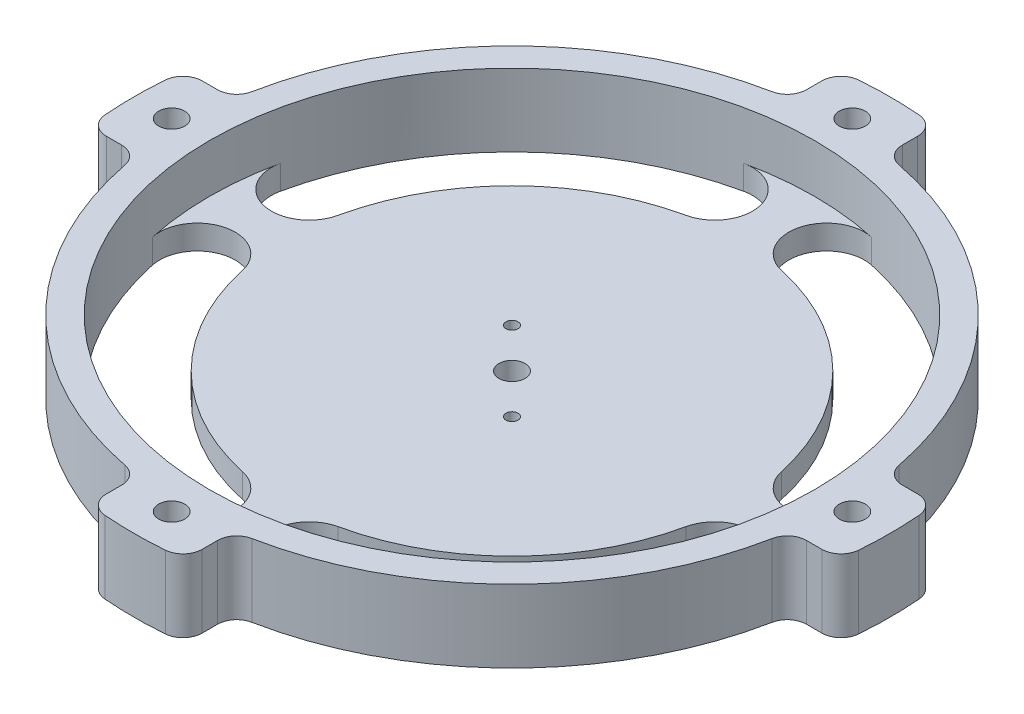
SolidWorks part; units mm, degrees
material "Nylon 101"
ref_plane "Front Plane" through (0, 0, 0) normal (0, 0, 1) x (1, 0, 0)
ref_plane "Top Plane" through (0, 0, 0) normal (0, 1, 0) x (1, 0, 0)
ref_plane "Right Plane" through (0, 0, 0) normal (1, 0, 0) x (0, 0, -1)
sketch "Sketch1" plane through (0, 0, 0) normal (0, 0, 1) x (1, 0, 0)
  line L0 (0, 0) -> (0, 12) construction
  line L1 (0, 0) -> (62.5, 0)
  line L2 (62.5, 0) -> (62.5, 12)
  line L3 (62.5, 12) -> (50, 12)
  line L4 (50, 12) -> (50, 4)
  line L5 (50, 4) -> (0, 4)
  line L6 (0, 4) -> (0, 0)
  dimension "D1" = 100
  dimension "D2" = 4
  dimension "D3" = 125
  dimension "D4" = 12
revolve "Revolve1" add sketch "Sketch1" angle 360 about L0
sketch "Sketch2" plane through (0, 4, 0) normal (0, 1, 0) x (1, 0, 0)
  line L0 (6.5407, -6.5407) -> (-6.5407, 6.5407) construction
  line L1 (0, 0) -> (-6.5407, 0) construction
  circle A0 centre (0, 0) radius 2
  circle A1 centre (6.5407, -6.5407) radius 1
  circle A2 centre (-6.5407, 6.5407) radius 1
  dimension "D1" = 4
  dimension "D3" = 2
  dimension "D2" = 18.5
  dimension "D4" = 45
extrude "Cut-Extrude1" cut sketch "Sketch2" against normal up to next
sketch "Sketch3" plane through (0, 4, 0) normal (0, 1, 0) x (1, 0, 0)
  line L0 (0, 0) -> (0, 62.5) construction
  line L1 (0, 0) -> (62.5, 0) construction
  line L2 (3, 42.761) -> (0, 42.761) construction
  line L3 (42.761, 3) -> (42.761, 0) construction
  circle A0 centre (0, 0) radius 37.5 construction
  circle A1 centre (0, 0) radius 62.5 construction
  arc A2 (9.25, 42.761) -> (42.761, 9.25) centre (0, 0) cw construction
  arc A3 (48.8697, 10.5714) -> (10.5714, 48.8697) centre (0, 0) ccw
  arc A4 (36.6523, 7.9286) -> (7.9286, 36.6523) centre (0, 0) ccw
  arc A5 (36.6523, 7.9286) -> (48.8697, 10.5714) centre (42.761, 9.25) ccw
  arc A6 (10.5714, 48.8697) -> (7.9286, 36.6523) centre (9.25, 42.761) ccw
  circle A7 centre (0, 0) radius 50 construction
  arc A8 (-9.25, 42.761) -> (-42.761, 9.25) centre (0, 0) ccw construction
  arc A9 (-48.8697, 10.5714) -> (-10.5714, 48.8697) centre (0, 0) cw
  arc A10 (-36.6523, 7.9286) -> (-7.9286, 36.6523) centre (0, 0) cw
  arc A11 (-36.6523, 7.9286) -> (-48.8697, 10.5714) centre (-42.761, 9.25) cw
  arc A12 (-10.5714, 48.8697) -> (-7.9286, 36.6523) centre (-9.25, 42.761) cw
  arc A13 (9.25, -42.761) -> (42.761, -9.25) centre (0, 0) ccw construction
  arc A14 (48.8697, -10.5714) -> (10.5714, -48.8697) centre (0, 0) cw
  arc A15 (36.6523, -7.9286) -> (7.9286, -36.6523) centre (0, 0) cw
  arc A16 (36.6523, -7.9286) -> (48.8697, -10.5714) centre (42.761, -9.25) cw
  arc A17 (10.5714, -48.8697) -> (7.9286, -36.6523) centre (9.25, -42.761) cw
  arc A18 (-9.25, -42.761) -> (-42.761, -9.25) centre (0, 0) cw construction
  arc A19 (-48.8697, -10.5714) -> (-10.5714, -48.8697) centre (0, 0) ccw
  arc A20 (-36.6523, -7.9286) -> (-7.9286, -36.6523) centre (0, 0) ccw
  arc A21 (-36.6523, -7.9286) -> (-48.8697, -10.5714) centre (-42.761, -9.25) ccw
  arc A22 (-10.5714, -48.8697) -> (-7.9286, -36.6523) centre (-9.25, -42.761) ccw
  point P10 (30.9359, 30.9359)
  point P15 (3, 42.761)
  point P24 (-30.9359, 30.9359)
  point P31 (30.9359, -30.9359)
  point P38 (-30.9359, -30.9359)
  dimension "D1" = 75
  dimension "D2" = 6
extrude "Cut-Extrude2" cut sketch "Sketch3" against normal up to next
hole_wizard "#18 (0.1695) Diameter Hole1" positions "Sketch5" profile "Sketch4" hole size "#18" standard "ANSI Inch" end condition up to next
sketch "Sketch5" plane through (0, 12, 0) normal (0, 1, 0) x (1, 0, 0)
  line L0 (0, 50) -> (0, 62.5) construction
  circle A0 centre (0, 0) radius 50 construction
  circle A1 centre (0, 0) radius 62.5 construction
  point P10 (0, 56.25)
  point P17 (56.25, 0)
  point P18 (0, -56.25)
  point P19 (-56.25, 0)
  point P20 (0, 0)
  dimension "D1" = 4
sketch "Sketch4" plane through (0, 12, -56.25) normal (1, 0, 0) x (0, 0, 1)
  line L0 (0, 0) -> (0, 12)
  line L1 (0, 12) -> (2.1526, 12)
  line L2 (2.1526, 12) -> (2.1526, 0)
  line L5 (2.1526, 0) -> (0, 0)
  line L11 (0, -6.35) -> (0, 107.95) construction
  dimension "Thru Hole Dia." = 4.3053
  dimension "Thru Hole Depth" = 12
extrude "Cut-Extrude3" cut sketch "Sketch6" against normal blind 28
sketch "Sketch6" plane through (0, 19.9825, 0) normal (0, 1, 0) x (1, 0, 0)
  line L0 (0, 0) -> (0, 62.5) construction
  line L1 (0, 0) -> (-62.5, 0) construction
  line L2 (-44.1942, 44.1942) -> (-38.5373, 38.5373) construction
  line L3 (-56.5976, 7.921) -> (-59.1349, 7.921)
  line L4 (-7.921, 56.5976) -> (-7.921, 59.1349)
  line L5 (7.921, 56.5976) -> (7.921, 59.1349)
  line L6 (56.5976, 7.921) -> (59.1349, 7.921)
  line L7 (56.5976, -7.921) -> (59.1349, -7.921)
  line L8 (7.921, -56.5976) -> (7.921, -59.1349)
  line L9 (-7.921, -56.5976) -> (-7.921, -59.1349)
  line L10 (-56.5976, -7.921) -> (-59.1349, -7.921)
  arc A0 (-62.2997, 5) -> (-5, 62.2997) centre (0, 0) cw
  arc A2 (-53.4819, 10.4852) -> (-56.5976, 7.921) centre (-56.5976, 11.096) cw
  arc A3 (-10.4852, 53.4819) -> (-7.921, 56.5976) centre (-11.096, 56.5976) ccw
  arc A4 (-53.4819, 10.4852) -> (-10.4852, 53.4819) centre (0, 0) cw
  arc A5 (-7.921, 59.1349) -> (-5, 62.2997) centre (-4.746, 59.1349) cw
  arc A6 (-59.1349, 7.921) -> (-62.2997, 5) centre (-59.1349, 4.746) ccw
  arc A7 (5, 62.2997) -> (62.2997, 5) centre (0, 0) cw
  arc A8 (7.921, 59.1349) -> (5, 62.2997) centre (4.746, 59.1349) ccw
  arc A9 (10.4852, 53.4819) -> (7.921, 56.5976) centre (11.096, 56.5976) cw
  arc A10 (10.4852, 53.4819) -> (53.4819, 10.4852) centre (0, 0) cw
  arc A11 (53.4819, 10.4852) -> (56.5976, 7.921) centre (56.5976, 11.096) ccw
  arc A12 (59.1349, 7.921) -> (62.2997, 5) centre (59.1349, 4.746) cw
  arc A13 (62.2997, -5) -> (5, -62.2997) centre (0, 0) cw
  arc A14 (59.1349, -7.921) -> (62.2997, -5) centre (59.1349, -4.746) ccw
  arc A15 (53.4819, -10.4852) -> (56.5976, -7.921) centre (56.5976, -11.096) cw
  arc A16 (53.4819, -10.4852) -> (10.4852, -53.4819) centre (0, 0) cw
  arc A17 (10.4852, -53.4819) -> (7.921, -56.5976) centre (11.096, -56.5976) ccw
  arc A18 (7.921, -59.1349) -> (5, -62.2997) centre (4.746, -59.1349) cw
  arc A19 (-5, -62.2997) -> (-62.2997, -5) centre (0, 0) cw
  arc A20 (-7.921, -59.1349) -> (-5, -62.2997) centre (-4.746, -59.1349) ccw
  arc A21 (-10.4852, -53.4819) -> (-7.921, -56.5976) centre (-11.096, -56.5976) cw
  arc A22 (-10.4852, -53.4819) -> (-53.4819, -10.4852) centre (0, 0) cw
  arc A23 (-53.4819, -10.4852) -> (-56.5976, -7.921) centre (-56.5976, -11.096) ccw
  arc A24 (-59.1349, -7.921) -> (-62.2997, -5) centre (-59.1349, -4.746) cw
  point P60 (0, 0)
